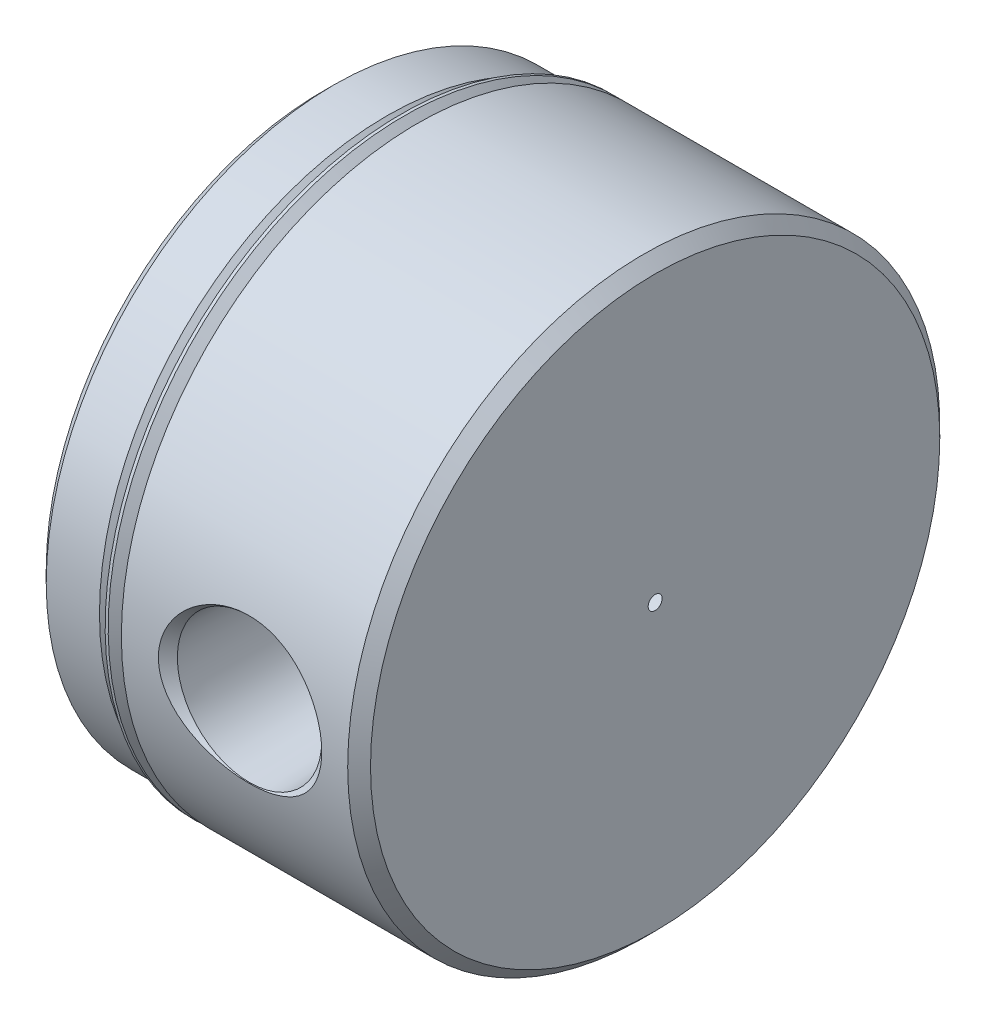
SolidWorks part; units mm, degrees
material "AISI 304"
ref_plane "Front Plane" through (0, 0, 0) normal (0, 0, 1) x (1, 0, 0)
ref_plane "Top Plane" through (0, 0, 0) normal (0, 1, 0) x (1, 0, 0)
ref_plane "Right Plane" through (0, 0, 0) normal (1, 0, 0) x (0, 0, -1)
ref_plane "Plane1" through (44.45, 0, 0) normal (1, 0, 0) x (0, 0, -1)
sketch "Sketch1" plane through (0, 0, 0) normal (0, 0, 1) x (1, 0, 0)
  line L0 (0, 0) -> (0, 18.434)
  line L1 (0, 18.434) -> (0.762, 19.196)
  line L2 (0.762, 19.196) -> (4.318, 19.196)
  line L3 (4.318, 19.196) -> (5.334, 18.1801)
  line L4 (5.334, 18.1801) -> (6.35, 18.1801)
  line L5 (6.35, 18.1801) -> (6.35, 19.7676)
  line L6 (6.35, 19.7676) -> (21.463, 19.7676)
  line L7 (21.463, 19.7676) -> (22.225, 19.0055)
  line L8 (22.225, 19.0055) -> (22.225, 0)
  line L9 (22.225, 0) -> (0, 0)
  line L10 (22.225, 0) -> (0, 0) construction
revolve "Revolve1" add sketch "Sketch1" angle 360 about L10 reverse direction yes
ref_plane "Plane2" through (22.225, 0, 0) normal (1, 0, 0) x (0, 0, -1)
hole_wizard "Hole1" positions "Sketch3" profile "Sketch2" legacy
sketch "Sketch3" plane through (0, 0, 0) normal (-1, 0, 0) x (0, 0, 1)
  point P0 (0, 0)
sketch "Sketch2" plane through (0, 0, 0) normal (0, 1, 0) x (0, 0, 1)
  line L0 (0, 0) -> (0, 22.4936)
  line L1 (0, 22.4936) -> (6.7564, 18.5928)
  line L2 (6.7564, 18.5928) -> (6.7564, 0)
  line L4 (6.7564, 0) -> (0, 0)
  line L6 (0, 22.4936) -> (-6.7564, 18.5928) construction
  line L7 (0, -4.2442) -> (0, 117.3081) construction
  dimension "Diameter" = 13.5128
  dimension "Depth" = 18.5928
  dimension "Drill Angle" = 120
sketch "Sketch4" plane through (0, 0, 0) normal (0, 1, 0) x (1, 0, 0)
  line L0 (14.2748, 0) -> (18.8626, 0)
  line L1 (18.8626, 0) -> (18.8626, -11.7069)
  line L2 (18.8626, -11.7069) -> (19.0945, -19.1325)
  line L3 (19.0945, -19.1325) -> (19.7295, -19.7676)
  line L4 (19.7295, -19.7676) -> (14.2748, -19.7676)
  line L5 (14.2748, -19.7676) -> (14.2748, 0)
  line L6 (14.2748, -19.7676) -> (14.2748, 0) construction
revolve "Cut-Revolve1" cut sketch "Sketch4" angle 360 about L6 reverse direction yes
cosmetic thread "Cosmetic Thread1" parameters "D1"=6.9342, "D2"=10.287
sketch "Sketch5" plane through (0, 0, 0) normal (0, 0, 1) x (1, 0, 0)
  line L0 (0, 0) -> (0, 12.3063)
  line L1 (0, 12.3063) -> (6.35, 12.3063)
  line L2 (6.35, 12.3063) -> (6.35, 0)
  line L3 (6.35, 0) -> (0, 0)
  line L4 (6.35, 0) -> (0, 0) construction
revolve "Cut-Revolve2" cut sketch "Sketch5" angle 360 about L4 reverse direction yes
ref_plane "Plane3" through (5.334, 0, 0) normal (1, 0, 0) x (0, 0, -1)
sketch "Sketch6" plane through (0, 0, 0) normal (0, 0, 1) x (1, 0, 0)
  line L0 (5.2675, 19.6834) -> (6.2166, 18.7343)
  line L1 (6.2166, 18.5547) -> (5.842, 18.1801)
  line L2 (5.842, 18.1801) -> (5.334, 18.1801)
  line L3 (5.334, 18.1801) -> (5.334, 17.9261)
  line L4 (5.334, 17.9261) -> (6.35, 17.9261)
  line L5 (6.35, 17.9261) -> (6.35, 18.8883)
  line L6 (6.35, 18.8883) -> (5.4707, 19.7676)
  line L7 (5.4707, 19.7676) -> (5.2675, 19.7676)
  line L8 (5.2675, 19.7676) -> (5.2675, 19.6834)
  line L9 (6.35, 0) -> (5.334, 0) construction
  arc A0 (6.2166, 18.7343) -> (6.2166, 18.5547) centre (6.1268, 18.6445) cw
revolve "Revolve2" add sketch "Sketch6" angle 360 about L9 reverse direction yes
ref_plane "Plane4" through (44.6278, 0, 0) normal (1, 0, 0) x (0, 0, -1)
ref_plane "Plane5" through (24.6126, 0, 0) normal (1, 0, 0) x (0, 0, -1)
ref_plane "Plane6" through (38.1, 0, 0) normal (1, 0, 0) x (0, 0, -1)
ref_plane "Plane7" through (22.225, 0, 0) normal (1, 0, 0) x (0, 0, -1)
ref_plane "Plane8" through (22.225, 0, 0) normal (1, 0, 0) x (0, 0, -1)
ref_plane "Plane9" through (0, 0, 0) normal (0, 0, 1) x (1, 0, 0)
ref_plane "Plane10" through (0, 0, 0) normal (0, 0, 1) x (1, 0, 0)
ref_plane "Plane11" through (22.225, 0, 0) normal (1, 0, 0) x (0, 0, -1)
ref_plane "Plane12" through (24.6126, 0, 0) normal (1, 0, 0) x (0, 0, -1)
ref_plane "lovra1 XY" through (38.1, 0, 0) normal (1, 0, 0) x (0, 0, -1)
ref_plane "lovra1 XZ" through (0, 0, 0) normal (0, -1, 0) x (-1, 0, 0)
ref_plane "lovra1 YZ" through (0, 0, 0) normal (0, 0, -1) x (-1, 0, 0)
ref_axis "lovra1 X" through (38.1, 0, 80.9) along (0, 0, -1)
ref_axis "lovra1 Y" through (38.1, -50, 0) along (0, 1, 0)
ref_axis "lovra1 Z" through (80.9, 0, 0) along (-1, 0, 0)
sketch3d "lovra1"
  point P0 (38.1, 0, 0)
ref_plane "lovra2 XY" through (38.1, 0, 0) normal (1, 0, 0) x (0, 0, -1)
ref_plane "lovra2 XZ" through (0, 11.176, 0) normal (0, -1, 0) x (-1, 0, 0)
ref_plane "lovra2 YZ" through (0, 0, 0) normal (0, 0, -1) x (-1, 0, 0)
ref_axis "lovra2 X" through (38.1, 11.176, 80.9) along (0, 0, -1)
ref_axis "lovra2 Y" through (38.1, -50, 0) along (0, 1, 0)
ref_axis "lovra2 Z" through (80.9, 11.176, 0) along (-1, 0, 0)
sketch3d "lovra2"
  point P0 (38.1, 11.176, 0)
ref_plane "lovra21 XY" through (0, 0, 0) normal (1, 0, 0) x (0, 0, -1)
ref_plane "lovra21 XZ" through (0, 0, 0) normal (0, -1, 0) x (-1, 0, 0)
ref_plane "lovra21 YZ" through (0, 0, 5.2705) normal (0, 0, -1) x (-1, 0, 0)
ref_axis "lovra21 X" through (0, 0, 80.9) along (0, 0, -1)
ref_axis "lovra21 Y" through (0, -50, 5.2705) along (0, 1, 0)
ref_axis "lovra21 Z" through (80.9, 0, 5.2705) along (-1, 0, 0)
sketch3d "lovra21"
  point P0 (0, 0, 5.2705)
ref_plane "lovra22 XY" through (0, 0, 0) normal (1, 0, 0) x (0, 0, -1)
ref_plane "lovra22 XZ" through (0, 0, 0) normal (0, -1, 0) x (-1, 0, 0)
ref_plane "lovra22 YZ" through (0, 0, -5.2705) normal (0, 0, -1) x (-1, 0, 0)
ref_axis "lovra22 X" through (0, 0, 80.9) along (0, 0, -1)
ref_axis "lovra22 Y" through (0, -50, -5.2705) along (0, 1, 0)
ref_axis "lovra22 Z" through (80.9, 0, -5.2705) along (-1, 0, 0)
sketch3d "lovra22"
  point P0 (0, 0, -5.2705)
ref_plane "lovra3 XY" through (38.1, 0, 0) normal (1, 0, 0) x (0, 0, -1)
ref_plane "lovra3 XZ" through (0, -11.176, 0) normal (0, -1, 0) x (-1, 0, 0)
ref_plane "lovra3 YZ" through (0, 0, 0) normal (0, 0, -1) x (-1, 0, 0)
ref_axis "lovra3 X" through (38.1, -11.176, 80.9) along (0, 0, -1)
ref_axis "lovra3 Y" through (38.1, -50, 0) along (0, 1, 0)
ref_axis "lovra3 Z" through (80.9, -11.176, 0) along (-1, 0, 0)
sketch3d "lovra3"
  point P0 (38.1, -11.176, 0)
ref_plane "mbr XY" through (22.225, 0, 0) normal (1, 0, 0) x (0, 0, -1)
ref_plane "mbr XZ" through (0, 0, 0) normal (0, -1, 0) x (-1, 0, 0)
ref_plane "mbr YZ" through (0, 0, 0) normal (0, 0, -1) x (-1, 0, 0)
ref_axis "mbr X" through (22.225, 0, 80.9) along (0, 0, -1)
ref_axis "mbr Y" through (22.225, -50, 0) along (0, 1, 0)
ref_axis "mbr Z" through (80.9, 0, 0) along (-1, 0, 0)
sketch3d "mbr"
  point P0 (22.225, 0, 0)
ref_plane "olen XY" through (22.225, 0, 0) normal (1, 0, 0) x (0, 0, -1)
ref_plane "olen XZ" through (0, 0, 0) normal (0, -1, 0) x (-1, 0, 0)
ref_plane "olen YZ" through (0, 0, 0) normal (0, 0, -1) x (-1, 0, 0)
ref_axis "olen X" through (22.225, 0, 80.9) along (0, 0, -1)
ref_axis "olen Y" through (22.225, -50, 0) along (0, 1, 0)
ref_axis "olen Z" through (80.9, 0, 0) along (-1, 0, 0)
sketch3d "olen"
  point P0 (22.225, 0, 0)
ref_plane "port XY" through (0, 0, 0) normal (0, 0, 1) x (1, 0, 0)
ref_plane "port XZ" through (0, 0, 0) normal (0, -1, 0) x (-1, 0, 0)
ref_plane "port YZ" through (14.2748, 0, 0) normal (1, 0, 0) x (0, 0, -1)
ref_axis "port X" through (-80.9, 0, 0) along (1, 0, 0)
ref_axis "port Y" through (14.2748, -50, 0) along (0, 1, 0)
ref_axis "port Z" through (14.2748, 0, 80.9) along (0, 0, -1)
sketch3d "port"
  point P0 (14.2748, 0, 0)
ref_plane "port2 XY" through (22.225, 0, 0) normal (1, 0, 0) x (0, 0, -1)
ref_plane "port2 XZ" through (0, 0, 0) normal (0, -1, 0) x (-1, 0, 0)
ref_plane "port2 YZ" through (0, 0, 0) normal (0, 0, -1) x (-1, 0, 0)
ref_axis "port2 X" through (22.225, 0, 80.9) along (0, 0, -1)
ref_axis "port2 Y" through (22.225, -50, 0) along (0, 1, 0)
ref_axis "port2 Z" through (80.9, 0, 0) along (-1, 0, 0)
sketch3d "port2"
  point P0 (22.225, 0, 0)
ref_plane "to_nut XY" through (24.6126, 0, 0) normal (1, 0, 0) x (0, 0, -1)
ref_plane "to_nut XZ" through (0, 0, 0) normal (0, -1, 0) x (-1, 0, 0)
ref_plane "to_nut YZ" through (0, 0, 0) normal (0, 0, -1) x (-1, 0, 0)
ref_axis "to_nut X" through (24.6126, 0, 80.9) along (0, 0, -1)
ref_axis "to_nut Y" through (24.6126, -50, 0) along (0, 1, 0)
ref_axis "to_nut Z" through (80.9, 0, 0) along (-1, 0, 0)
sketch3d "to_nut"
  point P0 (24.6126, 0, 0)
ref_plane "to_nut1 XY" through (24.6126, 0, 0) normal (1, 0, 0) x (0, 0, -1)
ref_plane "to_nut1 XZ" through (0, 0, 0) normal (0, -1, 0) x (-1, 0, 0)
ref_plane "to_nut1 YZ" through (0, 0, 0) normal (0, 0, -1) x (-1, 0, 0)
ref_axis "to_nut1 X" through (24.6126, 0, 80.9) along (0, 0, -1)
ref_axis "to_nut1 Y" through (24.6126, -50, 0) along (0, 1, 0)
ref_axis "to_nut1 Z" through (80.9, 0, 0) along (-1, 0, 0)
sketch3d "to_nut1"
  point P0 (24.6126, 0, 0)
ref_plane "to_pin XY" through (0, 0, 0) normal (0, 0, 1) x (1, 0, 0)
ref_plane "to_pin XZ" through (0, 0, 0) normal (0, -1, 0) x (-1, 0, 0)
ref_plane "to_pin YZ" through (34.925, 0, 0) normal (1, 0, 0) x (0, 0, -1)
ref_axis "to_pin X" through (-80.9, 0, 0) along (1, 0, 0)
ref_axis "to_pin Y" through (34.925, -50, 0) along (0, 1, 0)
ref_axis "to_pin Z" through (34.925, 0, 80.9) along (0, 0, -1)
sketch3d "to_pin"
  point P0 (34.925, 0, 0)
ref_plane "to_tube XY" through (5.334, 0, 0) normal (1, 0, 0) x (0, 0, -1)
ref_plane "to_tube XZ" through (0, 0, 0) normal (0, -1, 0) x (-1, 0, 0)
ref_plane "to_tube YZ" through (0, 0, 0) normal (0, 0, -1) x (-1, 0, 0)
ref_axis "to_tube X" through (5.334, 0, 80.9) along (0, 0, -1)
ref_axis "to_tube Y" through (5.334, -50, 0) along (0, 1, 0)
ref_axis "to_tube Z" through (80.9, 0, 0) along (-1, 0, 0)
sketch3d "to_tube"
  point P0 (5.334, 0, 0)
